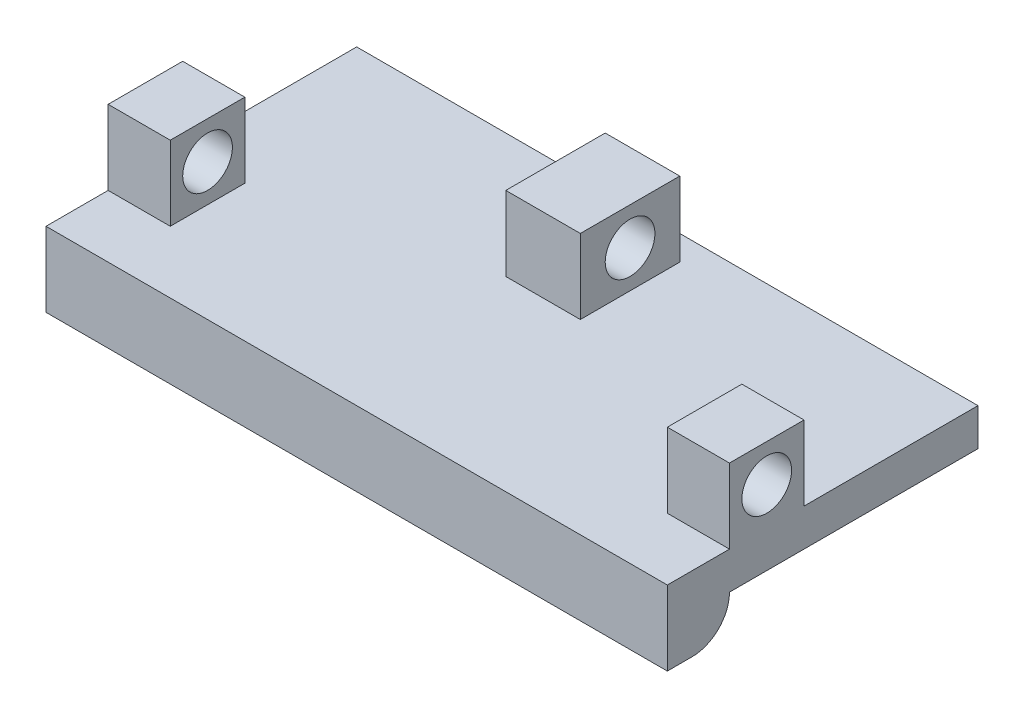
SolidWorks part; units mm, degrees
ref_plane "Front Plane" through (0, 0, 0) normal (0, 0, 1) x (1, 0, 0)
ref_plane "Top Plane" through (0, 0, 0) normal (0, 1, 0) x (1, 0, 0)
ref_plane "Right Plane" through (0, 0, 0) normal (1, 0, 0) x (0, 0, -1)
sketch "Sketch1" plane through (0, 0, 0) normal (0, 1, 0) x (1, 0, 0)
  line L0 (3, 12.5) -> (25, 12.5)
  line L1 (-25, 12.5) -> (-3, 12.5)
  line L2 (-25, 12.5) -> (-25, -12.5)
  line L3 (-25, -12.5) -> (25, -12.5)
  line L4 (25, 12.5) -> (25, -12.5)
  line L5 (-25, 12.5) -> (25, -12.5) construction
  line L6 (-25, -12.5) -> (25, 12.5) construction
  line L7 (-3, 2.5) -> (3, 2.5)
  line L8 (-3, 2.5) -> (-3, 10.5)
  line L9 (0, 7.5) -> (0, 0) construction
  line L10 (3, 2.5) -> (3, 10.5)
  line L11 (-3, 2.5) -> (3, 12.5) construction
  line L12 (-3, 12.5) -> (3, 2.5) construction
  line L13 (-3, 12.5) -> (3, 12.5)
  line L14 (3, 10.5) -> (-3, 10.5)
  point P0 (0, 0)
  point P6 (0, 7.5)
  dimension "D1" = 50
  dimension "D2" = 6
  dimension "D3" = 10
  dimension "D4" = 25
  dimension "D5" = 2
extrude "Boss-Extrude1" add sketch "Sketch1" along normal blind 3
sketch "Sketch2" plane through (0, 0, 0) normal (0, -1, 0) x (1, 0, 0)
  line L0 (-25, -12.5) -> (-25, 12.5) construction
  line L1 (25, 12.5) -> (-25, 12.5)
  line L2 (25, 12.5) -> (25, 7.5)
  line L3 (25, 7.5) -> (-25, 7.5)
  line L4 (-25, 12.5) -> (-25, 7.5)
  dimension "D1" = 5
extrude "Boss-Extrude2" add sketch "Sketch2" along normal blind 3
sketch "Sketch3" plane through (0, 3, 0) normal (0, 1, 0) x (1, 0, 0)
  line L0 (-25, 12.5) -> (-25, -12.5) construction
  line L1 (-25, -1.5) -> (-20, -1.5)
  line L2 (-25, -1.5) -> (-25, -7.5)
  line L3 (-25, -7.5) -> (-20, -7.5)
  line L4 (-20, -1.5) -> (-20, -7.5)
  line L5 (25, -12.5) -> (25, 12.5) construction
  line L6 (25, -1.5) -> (20, -1.5)
  line L7 (25, -1.5) -> (25, -7.5)
  line L8 (25, -7.5) -> (20, -7.5)
  line L9 (20, -1.5) -> (20, -7.5)
  line L10 (-25, -12.5) -> (25, -12.5) construction
  dimension "D1" = 5
  dimension "D2" = 6
  dimension "D3" = 5
extrude "Boss-Extrude3" add sketch "Sketch3" along normal blind 6
sketch "Sketch4" plane through (-25, 0, 0) normal (-1, 0, 0) x (0, 0, 1)
  line L0 (1.5, 3) -> (7.5, 9) construction
  circle A0 centre (4.5, 6) radius 2
  dimension "D1" = 4
extrude "Cut-Extrude1" cut sketch "Sketch4" against normal through all
sketch "Sketch5" plane through (0, 3, 0) normal (0, 1, 0) x (-1, 0, 0)
  line L1 (-3, -10.5) -> (3, -10.5)
  line L2 (-3, -10.5) -> (-3, -2.5)
  line L3 (-3, -2.5) -> (3, -2.5)
  line L4 (3, -10.5) -> (3, -2.5)
extrude "Boss-Extrude4" add sketch "Sketch5" along normal blind 6 and the other way blind 3
sketch "Sketch6" plane through (-3, 0, 0) normal (-1, 0, 0) x (0, 0, 1)
  line L0 (-10.5, 9) -> (-2.5, 3) construction
  line L1 (-2.5, 3) -> (-2.5, 9) construction
  circle A0 centre (-6.5, 6) radius 2
  dimension "D1" = 4
extrude "Cut-Extrude2" cut sketch "Sketch6" against normal blind 6
fillet "Fillet1" radius 3 1 edges at (0, -3, 7.5)
